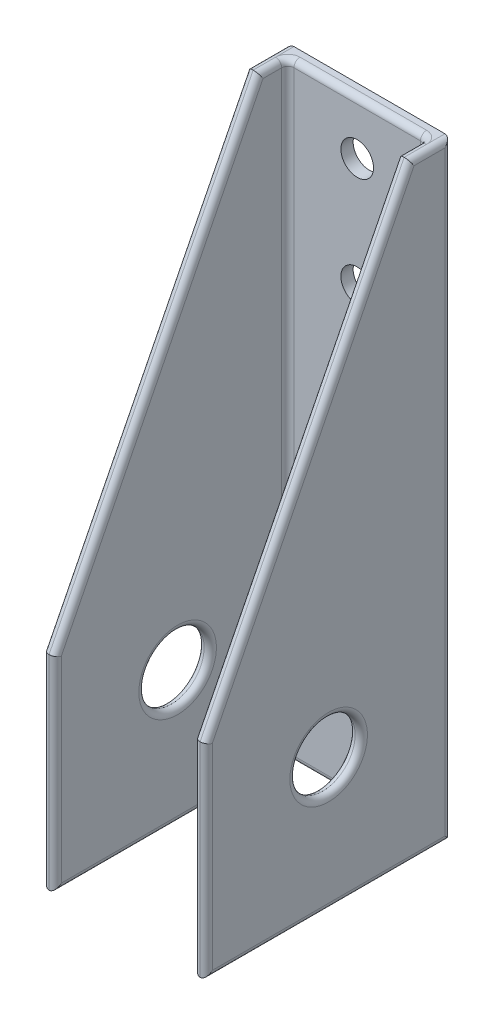
SolidWorks part; units mm, degrees
ref_plane "Płaszczyzna przednia" through (0, 0, 0) normal (0, 0, 1) x (1, 0, 0)
ref_plane "Płaszczyzna górna" through (0, 0, 0) normal (0, 1, 0) x (1, 0, 0)
ref_plane "Płaszczyzna prawa" through (0, 0, 0) normal (1, 0, 0) x (0, 0, -1)
sketch "Szkic1" plane through (0, 0, 0) normal (0, 0, 1) x (1, 0, 0)
  line L1 (20, -74.5) -> (-20, -74.5)
  line L2 (20, -74.5) -> (20, 74.5)
  line L3 (20, 74.5) -> (-20, 74.5)
  line L4 (-20, -74.5) -> (-20, 74.5)
  line L5 (20, -74.5) -> (-20, 74.5) construction
  line L6 (20, 74.5) -> (-20, -74.5) construction
  point P0 (0, 0)
  dimension "D1" = 40
  dimension "D2" = 149
extrude "Dodanie-wyciągnięcie1" add sketch "Szkic1" along normal blind 60
sketch "Szkic2" plane through (0, 74.5, 0) normal (0, 1, 0) x (1, 0, 0)
  line L0 (20, -60) -> (-20, -60) construction
  line L1 (-17, -60) -> (17, -60)
  line L2 (-17, -60) -> (-17, -3)
  line L3 (-17, -3) -> (17, -3)
  line L4 (17, -60) -> (17, -3)
  line L5 (20, 0) -> (-20, 0) construction
  line L6 (-20, -60) -> (-20, 0) construction
  line L7 (20, -60) -> (20, 0) construction
  dimension "D1" = 3
  dimension "D2" = 3
  dimension "D3" = 3
extrude "Wytnij-wyciągnięcie1" cut sketch "Szkic2" against normal through all
sketch "Szkic4" plane through (-20, 0, 0) normal (-1, 0, 0) x (0, 0, 1)
  line L0 (60, -74.5) -> (0, -74.5) construction
  line L2 (0, 74.5) -> (0, -74.5) construction
  line L3 (60, -24.5) -> (10, 74.5)
  line L4 (60, 74.5) -> (60, -74.5) construction
  line L5 (60, 74.5) -> (0, 74.5) construction
  circle A0 centre (30, -42) radius 8
  line M4 (60, -74.5) -> (60, 74.5)
  line M5 (60, 74.5) -> (0, 74.5)
  dimension "D3" = 16
  dimension "D1" = 32.5
  dimension "D2" = 30
  dimension "D4" = 50
  dimension "D5" = 10
extrude "Wytnij-wyciągnięcie2" cut sketch "Szkic4" against normal blind 45 contours L3 M4 M5 | A0 region at (-20, 41.5, 43.3333) region at (-20, -42, 30)
sketch "Szkic5" plane through (0, 0, 3) normal (0, 0, 1) x (1, 0, 0)
  line L0 (17, 74.5) -> (-17, 74.5) construction
  circle A0 centre (0, 61.5) radius 4
  circle A1 centre (0, 34.5) radius 4
  circle A2 centre (0, 7.5) radius 4
  point P9 (0, 74.5)
  dimension "D1" = 8
  dimension "D2" = 8
  dimension "D3" = 8
  dimension "D4" = 13
  dimension "D5" = 27
  dimension "D6" = 27
extrude "Wytnij-wyciągnięcie3" cut sketch "Szkic5" against normal through all
fillet "Zaokrąglenie1" radius 1.5 26 edges at (0, 74.5, 3) (0, -74.5, 3) (20, 74.5, 5) (20, 0, 0) (20, -74.5, 30) (20, -49.5, 60) (20, 25, 35) (20, -42, 38) (17, -49.5, 60) (17, -74.5, 31.5) (17, 0, 3) (17, 74.5, 6.5) (17, 25, 35) (17, -42, 22) (-17, 74.5, 6.5) (-17, 0, 3) (-17, -74.5, 31.5) (-17, -49.5, 60) (-17, 25, 35) (-17, -42, 38) (-20, -49.5, 60) (-20, -74.5, 30) (-20, 0, 0) (-20, 74.5, 5) (-20, 25, 35) (-20, -42, 38)
